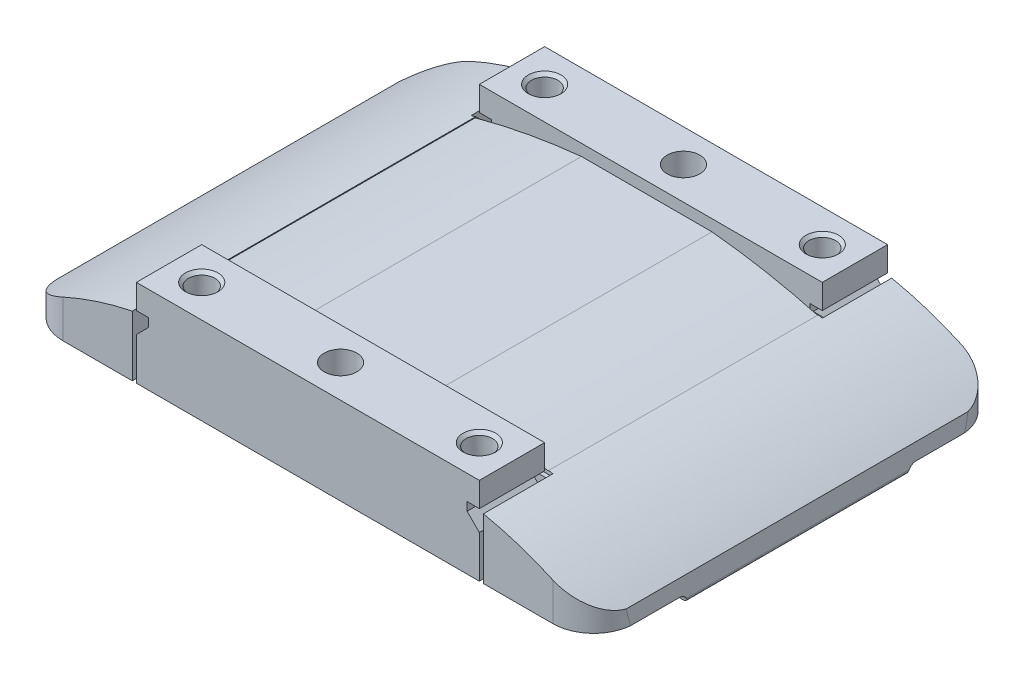
SolidWorks part; units mm, degrees
ref_plane "Front" through (0, 0, 0) normal (0, 0, 1) x (1, 0, 0)
ref_plane "Top" through (0, 0, 0) normal (0, 1, 0) x (1, 0, 0)
ref_plane "Right" through (0, 0, 0) normal (1, 0, 0) x (0, 0, -1)
ref_plane "Plane1" through (0, 0, 0) normal (0, 0, 1) x (1, 0, 0)
sketch "Sketch1" plane through (0, 0, 0) normal (0, 0, 1) x (1, 0, 0)
  line L0 (-34.5, 0.2) -> (-31.366, 0.2)
  line L1 (-31.366, 0.2) -> (-30.5, 0.7)
  line L2 (-30.5, 0.7) -> (-21, 0.7)
  line L3 (-21, 0.7) -> (-21, 0)
  line L4 (-21, 0) -> (21, 0)
  line L5 (21, 0) -> (21, 0.7)
  line L6 (21, 0.7) -> (30.5, 0.7)
  line L7 (30.5, 0.7) -> (31.366, 0.2)
  line L8 (31.366, 0.2) -> (34.5, 0.2)
  line L9 (35, 0.7) -> (34.9133, 3.183)
  line L10 (21, 8.6968) -> (21, 11.9)
  line L11 (21, 11.9) -> (-21, 11.9)
  line L12 (-21, 11.9) -> (-21, 8.6968)
  line L13 (-34.9133, 3.183) -> (-35, 0.7)
  arc A0 (-35, 0.7) -> (-34.5, 0.2) centre (-34.5, 0.7) ccw
  arc A1 (34.5, 0.2) -> (35, 0.7) centre (34.5, 0.7) ccw
  arc A2 (34.9133, 3.183) -> (21, 8.6968) centre (13.48, -30.59) ccw
  arc A3 (-21, 8.6968) -> (-34.9133, 3.183) centre (-13.48, -30.59) ccw
extrude "Boss-Extrude1" add sketch "Sketch1" against normal blind 25 and the other way blind 25
ref_plane "Plane2" through (0, 0, 0) normal (0, 0, 1) x (1, 0, 0)
sketch "Sketch2" plane through (0, 0, 0) normal (0, 0, 1) x (1, 0, 0)
  line L0 (21, 8.5946) -> (21, 30)
  line L1 (21, 30) -> (-21, 30)
  line L2 (-21, 30) -> (-21, 8.5946)
  arc A0 (-21, 8.5946) -> (21, 8.5946) centre (0, -68.6) cw
extrude "Cut-Extrude1" cut sketch "Sketch2" against normal blind 17 and the other way blind 17
ref_plane "Plane3" through (0, 0, 25) normal (0, 0, 1) x (1, 0, 0)
sketch "Sketch3" plane through (0, 0, 25) normal (0, 0, 1) x (1, 0, 0)
  line L0 (-21.5, -3) -> (-21, -3)
  line L1 (-21, -3) -> (-21, 6.37)
  line L2 (-21, 6.37) -> (-19.5, 7.87)
  line L3 (-19.5, 7.87) -> (-19.5, 8.9)
  line L4 (-19.5, 8.9) -> (-21, 8.9)
  line L5 (-21, 8.9) -> (-21, 11.9)
  line L6 (-21, 11.9) -> (21, 11.9)
  line L7 (21, 11.9) -> (21, 8.9)
  line L8 (21, 8.9) -> (19.5, 8.9)
  line L9 (19.5, 8.9) -> (19.5, 7.87)
  line L10 (19.5, 7.87) -> (21, 6.37)
  line L11 (21, 6.37) -> (21, -3)
  line L12 (21, -3) -> (21.5, -3)
  line L13 (21.5, -3) -> (21.5, 16.9)
  line L14 (21.5, 16.9) -> (-21.5, 16.9)
  line L15 (-21.5, 16.9) -> (-21.5, -3)
extrude "Cut-Extrude2" cut sketch "Sketch3" against normal blind 8
ref_plane "Plane4" through (0, 0, -25) normal (0, 0, 1) x (1, 0, 0)
sketch "Sketch4" plane through (0, 0, -25) normal (0, 0, 1) x (1, 0, 0)
  line L0 (-21.5, -3) -> (-21, -3)
  line L1 (-21, -3) -> (-21, 6.37)
  line L2 (-21, 6.37) -> (-19.5, 7.87)
  line L3 (-19.5, 7.87) -> (-19.5, 8.9)
  line L4 (-19.5, 8.9) -> (-21, 8.9)
  line L5 (-21, 8.9) -> (-21, 11.9)
  line L6 (-21, 11.9) -> (21, 11.9)
  line L7 (21, 11.9) -> (21, 8.9)
  line L8 (21, 8.9) -> (19.5, 8.9)
  line L9 (19.5, 8.9) -> (19.5, 7.87)
  line L10 (19.5, 7.87) -> (21, 6.37)
  line L11 (21, 6.37) -> (21, -3)
  line L12 (21, -3) -> (21.5, -3)
  line L13 (21.5, -3) -> (21.5, 16.9)
  line L14 (21.5, 16.9) -> (-21.5, 16.9)
  line L15 (-21.5, 16.9) -> (-21.5, -3)
extrude "Cut-Extrude3" cut sketch "Sketch4" along normal blind 8
ref_plane "Plane5" through (0, 0, 0) normal (1, 0, 0) x (0, 0, -1)
sketch "Sketch5" plane through (0, 0, 0) normal (1, 0, 0) x (0, 0, -1)
  line L0 (-17, 8.25) -> (-16.5, 8.25)
  line L1 (-16.5, 8.25) -> (-16.5, 11)
  line L2 (-16.5, 11) -> (16.5, 11)
  line L3 (16.5, 11) -> (16.5, 8.25)
  line L4 (16.5, 8.25) -> (17, 8.25)
  line L5 (17, 8.25) -> (17, 12)
  line L6 (17, 12) -> (-17, 12)
  line L7 (-17, 12) -> (-17, 8.25)
extrude "Cut-Extrude4" cut sketch "Sketch5" against normal blind 21.5 and the other way blind 21.5
ref_plane "Plane6" through (0, 0, 0) normal (1, 0, 0) x (0, 0, -1)
sketch "Sketch6" plane through (0, 0, 0) normal (1, 0, 0) x (0, 0, -1)
  line L0 (-30, 1.2) -> (-30, -5)
  line L1 (-30, -5) -> (30, -5)
  line L2 (30, -5) -> (30, 1.2)
  line L3 (30, 1.2) -> (14.5, 1.2)
  line L4 (13.5, 0.2) -> (13.5, -2)
  line L5 (13.5, -2) -> (-13.5, -2)
  line L6 (-13.5, -2) -> (-13.5, 0.2)
  line L7 (-14.5, 1.2) -> (-30, 1.2)
  arc A0 (14.5, 1.2) -> (13.5, 0.2) centre (14.5, 0.2) ccw
  arc A1 (-13.5, 0.2) -> (-14.5, 1.2) centre (-14.5, 0.2) ccw
extrude "Cut-Extrude5" cut sketch "Sketch6" against normal blind 35 and the other way blind 35
ref_plane "Plane7" through (0, 0, 0) normal (0, 1, 0) x (-1, 0, 0)
sketch "Sketch7" plane through (0, 0, 0) normal (0, 1, 0) x (-1, 0, 0)
  line L0 (51.7619, -32.7548) -> (51.7619, 37.1837)
  line L1 (51.7619, 37.1837) -> (-56.0062, 37.1837)
  line L2 (-56.0062, 37.1837) -> (-56.0062, -32.7548)
  line L3 (-56.0062, -32.7548) -> (51.7619, -32.7548)
  line L4 (35, -20) -> (35, 20)
  line L5 (30, 25) -> (-30, 25)
  line L6 (-35, 20) -> (-35, -20)
  line L7 (-30, -25) -> (30, -25)
  arc A0 (35, 20) -> (30, 25) centre (30, 20) ccw
  arc A1 (-30, 25) -> (-35, 20) centre (-30, 20) ccw
  arc A2 (-35, -20) -> (-30, -25) centre (-30, -20) ccw
  arc A3 (30, -25) -> (35, -20) centre (30, -20) ccw
extrude "Cut-Extrude6" cut sketch "Sketch7" against normal blind 29 and the other way blind 29
ref_plane "Plane8" through (0, 0, 21) normal (0, 0, 1) x (1, 0, 0)
sketch "Sketch8" plane through (0, 0, 21) normal (0, 0, 1) x (1, 0, 0)
  line L0 (-17, 2.3641) -> (-18.621, 3.3)
  line L1 (-18.621, 3.3) -> (-18.621, 11.521)
  line L2 (-18.621, 11.521) -> (-19, 11.9)
  line L3 (-19, 11.9) -> (-17, 11.9)
  line L4 (-17, 11.9) -> (-17, 2.3641)
  line L5 (-17, 11.9) -> (-17, 2.3641) construction
revolve "Cut-Revolve1" cut sketch "Sketch8" angle 360 about L5 reverse direction yes
ref_plane "Plane9" through (0, 0, -21) normal (0, 0, 1) x (1, 0, 0)
sketch "Sketch9" plane through (0, 0, -21) normal (0, 0, 1) x (1, 0, 0)
  line L0 (-17, 2.3641) -> (-18.621, 3.3)
  line L1 (-18.621, 3.3) -> (-18.621, 11.521)
  line L2 (-18.621, 11.521) -> (-19, 11.9)
  line L3 (-19, 11.9) -> (-17, 11.9)
  line L4 (-17, 11.9) -> (-17, 2.3641)
  line L5 (-17, 11.9) -> (-17, 2.3641) construction
revolve "Cut-Revolve2" cut sketch "Sketch9" angle 360 about L5 reverse direction yes
ref_plane "Plane10" through (0, 0, -21) normal (0, 0, 1) x (1, 0, 0)
sketch "Sketch10" plane through (0, 0, -21) normal (0, 0, 1) x (1, 0, 0)
  line L0 (17, 2.3641) -> (15.379, 3.3)
  line L1 (15.379, 3.3) -> (15.379, 11.521)
  line L2 (15.379, 11.521) -> (15, 11.9)
  line L3 (15, 11.9) -> (17, 11.9)
  line L4 (17, 11.9) -> (17, 2.3641)
  line L5 (17, 11.9) -> (17, 2.3641) construction
revolve "Cut-Revolve3" cut sketch "Sketch10" angle 360 about L5 reverse direction yes
ref_plane "Plane11" through (0, 0, 21) normal (0, 0, 1) x (1, 0, 0)
sketch "Sketch11" plane through (0, 0, 21) normal (0, 0, 1) x (1, 0, 0)
  line L0 (17, 2.3641) -> (15.379, 3.3)
  line L1 (15.379, 3.3) -> (15.379, 11.521)
  line L2 (15.379, 11.521) -> (15, 11.9)
  line L3 (15, 11.9) -> (17, 11.9)
  line L4 (17, 11.9) -> (17, 2.3641)
  line L5 (17, 11.9) -> (17, 2.3641) construction
revolve "Cut-Revolve4" cut sketch "Sketch11" angle 360 about L5 reverse direction yes
ref_plane "Plane12" through (0, 0, 21) normal (0, 0, 1) x (1, 0, 0)
sketch "Sketch12" plane through (0, 0, 21) normal (0, 0, 1) x (1, 0, 0)
  line L0 (0, 4.7453) -> (-2, 5.9)
  line L1 (-2, 5.9) -> (-2, 11.9)
  line L2 (-2, 11.9) -> (0, 11.9)
  line L3 (0, 11.9) -> (0, 4.7453)
  line L4 (0, 11.9) -> (0, 4.7453) construction
revolve "Cut-Revolve5" cut sketch "Sketch12" angle 360 about L4 reverse direction yes
ref_plane "Plane13" through (0, 0, -21) normal (0, 0, 1) x (1, 0, 0)
sketch "Sketch13" plane through (0, 0, -21) normal (0, 0, 1) x (1, 0, 0)
  line L0 (0, 4.7453) -> (-2, 5.9)
  line L1 (-2, 5.9) -> (-2, 11.9)
  line L2 (-2, 11.9) -> (0, 11.9)
  line L3 (0, 11.9) -> (0, 4.7453)
  line L4 (0, 11.9) -> (0, 4.7453) construction
revolve "Cut-Revolve6" cut sketch "Sketch13" angle 360 about L4 reverse direction yes
